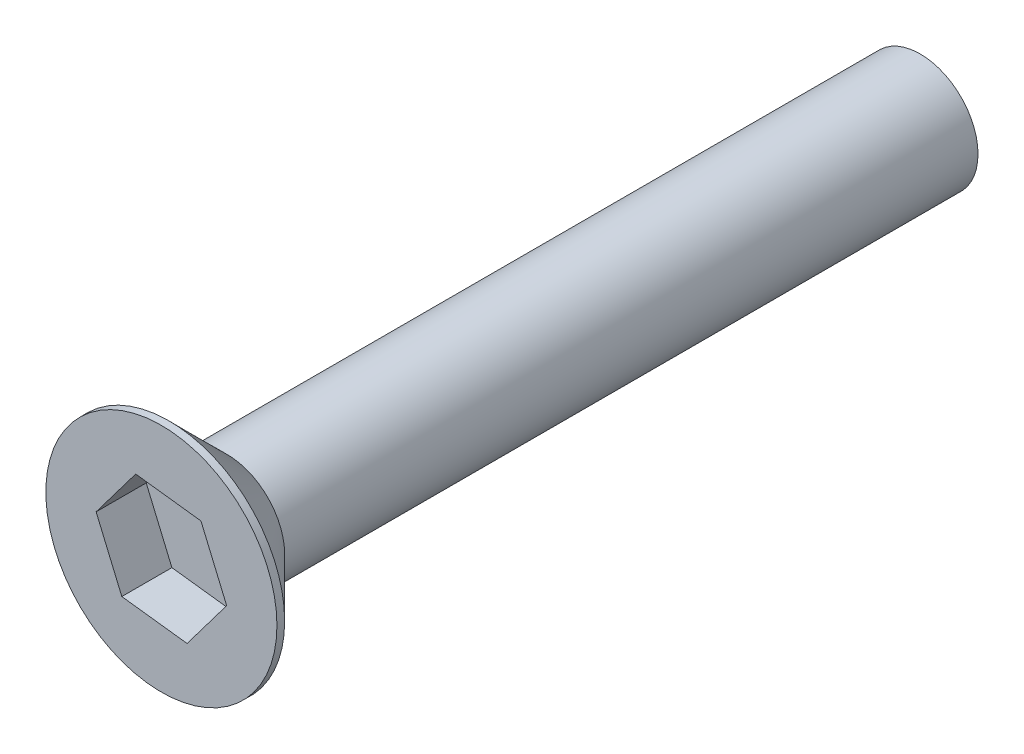
SolidWorks part; units mm, degrees
ref_plane "Front Plane" through (0, 0, 0) normal (0, 0, 1) x (1, 0, 0)
ref_plane "Top Plane" through (0, 0, 0) normal (0, 1, 0) x (1, 0, 0)
ref_plane "Right Plane" through (0, 0, 0) normal (1, 0, 0) x (0, 0, -1)
sketch "Sketch1" plane through (0, 0, 0) normal (0, 0, 1) x (1, 0, 0)
  circle A0 centre (0, 0) radius 1.5
  dimension "D1" = 3
extrude "Boss-Extrude1" add sketch "Sketch1" along normal blind 18
sketch "Sketch2" plane through (0, 0, 18) normal (0, 0, 1) x (1, 0, 0)
  circle A0 centre (0, 0) radius 3
  dimension "D1" = 6
extrude "Boss-Extrude2" add sketch "Sketch2" along normal blind 1.7
chamfer "Chamfer1" distance 1.5 angle 45 1 edges at (3, 0, 18)
sketch "Sketch7" plane through (0, 0, 19.7) normal (0, 0, 1) x (1, 0, 0)
  line L1 (0.6672, -1.5714) -> (1.6945, -0.2079)
  line L2 (1.6945, -0.2079) -> (1.0273, 1.3635)
  line L3 (1.0273, 1.3635) -> (-0.6672, 1.5714)
  line L4 (-0.6672, 1.5714) -> (-1.6945, 0.2079)
  line L5 (-1.6945, 0.2079) -> (-1.0273, -1.3635)
  line L6 (-1.0273, -1.3635) -> (0.6672, -1.5714)
  circle A0 centre (0, 0) radius 1.4785 construction
extrude "Cut-Extrude1" cut sketch "Sketch7" against normal blind 1.3
